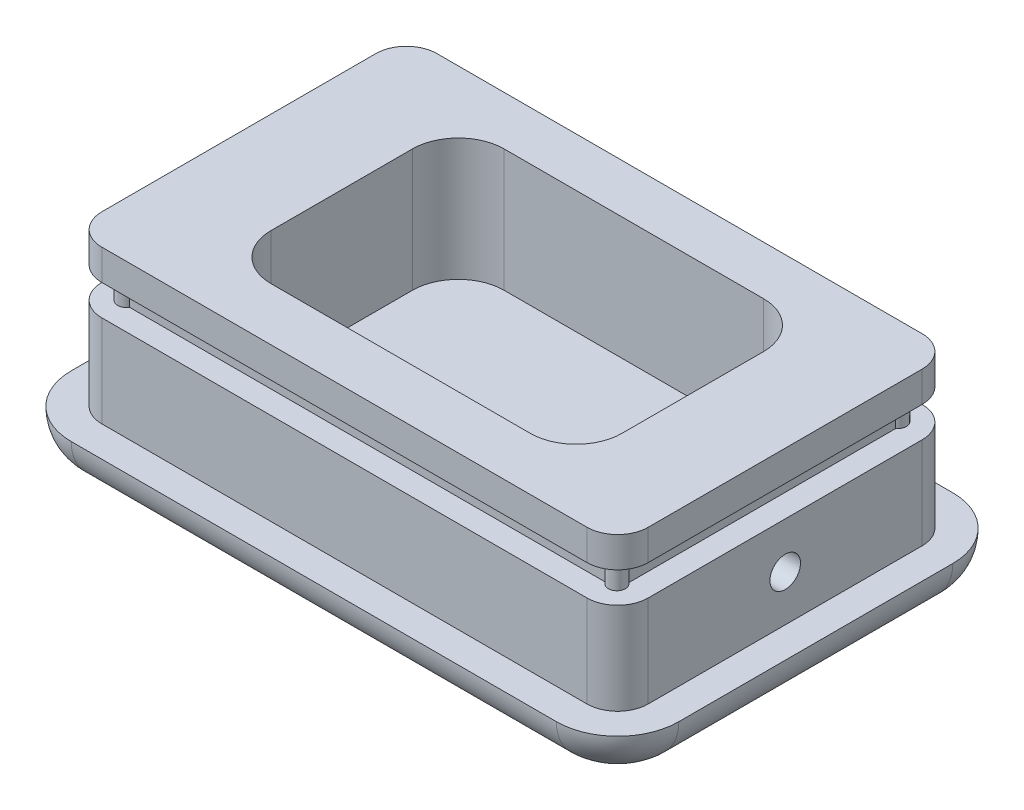
SolidWorks part; units mm, degrees
ref_plane "Alzado" through (0, 0, 0) normal (0, 0, 1) x (1, 0, 0)
ref_plane "Planta" through (0, 0, 0) normal (0, 1, 0) x (1, 0, 0)
ref_plane "Vista lateral" through (0, 0, 0) normal (1, 0, 0) x (0, 0, -1)
sketch "Croquis1" plane through (0, 0, 0) normal (0, 1, 0) x (1, 0, 0)
  line L0 (0, 47.449) -> (0, -64.3311) construction
  line L1 (-97.328, 0) -> (118.047, 0) construction
  line L7 (-15.85, -12.95) -> (15.85, -12.95)
  line L8 (-19.85, -8.95) -> (-19.85, 8.95)
  line L9 (-15.85, 12.95) -> (15.85, 12.95)
  line L10 (19.85, -8.95) -> (19.85, 8.95)
  line L11 (-19.85, -12.95) -> (19.85, 12.95) construction
  line L12 (-19.85, 12.95) -> (19.85, -12.95) construction
  arc A4 (15.85, 12.95) -> (19.85, 8.95) centre (15.85, 8.95) cw
  arc A5 (15.85, -12.95) -> (19.85, -8.95) centre (15.85, -8.95) ccw
  arc A6 (-15.85, -12.95) -> (-19.85, -8.95) centre (-15.85, -8.95) cw
  arc A7 (-19.85, 8.95) -> (-15.85, 12.95) centre (-15.85, 8.95) cw
  point P5 (0, 0)
  dimension "D2" = 25.9
  dimension "D3" = 4
  dimension "D1" = 39.7
extrude "Saliente-Extruir1" add sketch "Croquis1" along normal blind 3
sketch "Croquis2" plane through (0, 3, 0) normal (0, 1, 0) x (1, 0, 0)
  line L0 (15.85, 10.95) -> (-15.85, 10.95)
  line L1 (-17.85, 8.95) -> (-17.85, -8.95)
  line L2 (-15.85, -10.95) -> (15.85, -10.95)
  line L3 (17.85, -8.95) -> (17.85, 8.95)
  line L8 (15.85, 11.25) -> (-15.85, 11.25)
  line L9 (-18.15, 8.95) -> (-18.15, -8.95)
  line L10 (-15.85, -11.25) -> (15.85, -11.25)
  line L11 (18.15, -8.95) -> (18.15, 8.95)
  line L12 (15.85, 11.25) -> (-15.85, 11.25) construction
  line L13 (-18.15, 8.95) -> (-18.15, -8.95) construction
  line L14 (-15.85, -11.25) -> (15.85, -11.25) construction
  line L15 (18.15, -8.95) -> (18.15, 8.95) construction
  arc A0 (17.85, 8.95) -> (15.85, 10.95) centre (15.85, 8.95) ccw
  arc A1 (-15.85, 10.95) -> (-17.85, 8.95) centre (-15.85, 8.95) ccw
  arc A2 (-17.85, -8.95) -> (-15.85, -10.95) centre (-15.85, -8.95) ccw
  arc A3 (15.85, -10.95) -> (17.85, -8.95) centre (15.85, -8.95) ccw
  arc A8 (18.15, 8.95) -> (15.85, 11.25) centre (15.85, 8.95) ccw
  arc A9 (-15.85, 11.25) -> (-18.15, 8.95) centre (-15.85, 8.95) ccw
  arc A10 (-18.15, -8.95) -> (-15.85, -11.25) centre (-15.85, -8.95) ccw
  arc A11 (15.85, -11.25) -> (18.15, -8.95) centre (15.85, -8.95) ccw
  arc A12 (18.15, 8.95) -> (15.85, 11.25) centre (15.85, 8.95) ccw construction
  arc A13 (-15.85, 11.25) -> (-18.15, 8.95) centre (-15.85, 8.95) ccw construction
  arc A14 (-18.15, -8.95) -> (-15.85, -11.25) centre (-15.85, -8.95) ccw construction
  arc A15 (15.85, -11.25) -> (18.15, -8.95) centre (15.85, -8.95) ccw construction
  dimension "D1" = 1.7
  dimension "D2" = 0.3
extrude "Saliente-Extruir3" add sketch "Croquis2" along normal blind 6 contours L2 A3 L3 A0 L0 A1 L1 A2
sketch "Croquis3" plane through (0, 9, 0) normal (0, 1, 0) x (1, 0, 0)
  line L8 (-15.85, -9.45) -> (15.85, -9.45)
  line L9 (16.35, -8.95) -> (16.35, 8.95)
  line L10 (15.85, 9.45) -> (-15.85, 9.45)
  line L11 (-16.35, 8.95) -> (-16.35, -8.95)
  line L12 (-15.85, -9.45) -> (15.85, -9.45)
  line L13 (16.35, -8.95) -> (16.35, 8.95)
  line L14 (15.85, 9.45) -> (-15.85, 9.45)
  line L15 (-16.35, 8.95) -> (-16.35, -8.95)
  arc A8 (15.85, -9.45) -> (16.35, -8.95) centre (15.85, -8.95) ccw
  arc A9 (16.35, 8.95) -> (15.85, 9.45) centre (15.85, 8.95) ccw
  arc A10 (-15.85, 9.45) -> (-16.35, 8.95) centre (-15.85, 8.95) ccw
  arc A11 (-16.35, -8.95) -> (-15.85, -9.45) centre (-15.85, -8.95) ccw
  arc A12 (15.85, -9.45) -> (16.35, -8.95) centre (15.85, -8.95) ccw
  arc A13 (16.35, 8.95) -> (15.85, 9.45) centre (15.85, 8.95) ccw
  arc A14 (-15.85, 9.45) -> (-16.35, 8.95) centre (-15.85, 8.95) ccw
  arc A15 (-16.35, -8.95) -> (-15.85, -9.45) centre (-15.85, -8.95) ccw
  dimension "D1" = 1.5
extrude "Saliente-Extruir4" add sketch "Croquis3" along normal blind 2
sketch "Croquis4" plane through (0, 11, 0) normal (0, 1, 0) x (1, 0, 0)
  line L4 (-15.85, -10.95) -> (15.85, -10.95)
  line L5 (17.85, -8.95) -> (17.85, 8.95)
  line L6 (15.85, 10.95) -> (-15.85, 10.95)
  line L7 (-17.85, 8.95) -> (-17.85, -8.95)
  line L8 (-15.85, -10.95) -> (15.85, -10.95)
  line L9 (17.85, -8.95) -> (17.85, 8.95)
  line L10 (15.85, 10.95) -> (-15.85, 10.95)
  line L11 (-17.85, 8.95) -> (-17.85, -8.95)
  arc A4 (15.85, -10.95) -> (17.85, -8.95) centre (15.85, -8.95) ccw
  arc A5 (17.85, 8.95) -> (15.85, 10.95) centre (15.85, 8.95) ccw
  arc A6 (-15.85, 10.95) -> (-17.85, 8.95) centre (-15.85, 8.95) ccw
  arc A7 (-17.85, -8.95) -> (-15.85, -10.95) centre (-15.85, -8.95) ccw
  arc A8 (15.85, -10.95) -> (17.85, -8.95) centre (15.85, -8.95) ccw
  arc A9 (17.85, 8.95) -> (15.85, 10.95) centre (15.85, 8.95) ccw
  arc A10 (-15.85, 10.95) -> (-17.85, 8.95) centre (-15.85, 8.95) ccw
  arc A11 (-17.85, -8.95) -> (-15.85, -10.95) centre (-15.85, -8.95) ccw
  dimension "D1" = 0
extrude "Saliente-Extruir5" add sketch "Croquis4" along normal blind 2
fillet "Redondeo1" radius 3 8 edges at (0, 0, -12.95) (-18.6784, 0, -11.7784) (-19.85, 0, 0) (-18.6784, 0, 11.7784) (0, 0, 12.95) (18.6784, 0, 11.7784) (19.85, 0, 0) (18.6784, 0, -11.7784)
sketch "Croquis5" plane through (-17.85, 0, 0) normal (-1, 0, 0) x (0, 0, 1)
  line L0 (0, 9) -> (0, 3) construction
  line L1 (-8.95, 9) -> (8.95, 9) construction
  line L2 (-8.95, 3) -> (8.95, 3) construction
  circle A0 centre (0, 6) radius 1
  dimension "D1" = 2
extrude "Cortar-Extruir1" cut sketch "Croquis5" against normal blind 5
sketch "Croquis6" plane through (17.85, 0, 0) normal (1, 0, 0) x (0, 0, -1)
  line L0 (0, 9) -> (0, 3) construction
  line L1 (-8.95, 9) -> (8.95, 9) construction
  line L2 (-8.95, 3) -> (8.95, 3) construction
  circle A0 centre (0, 6) radius 1
  dimension "D1" = 2
extrude "Cortar-Extruir2" cut sketch "Croquis6" against normal blind 5
sketch "Croquis8" plane through (0, 13, 0) normal (0, 1, 0) x (1, 0, 0)
  line L0 (-17.85, 0) -> (17.85, 0)
  line L1 (-17.85, 8.95) -> (-17.85, -8.95) construction
  line L2 (17.85, -8.95) -> (17.85, 8.95) construction
  line L3 (0, 10.95) -> (0, -10.95)
  line L4 (15.85, 10.95) -> (-15.85, 10.95) construction
  line L5 (-15.85, -10.95) -> (15.85, -10.95) construction
  arc A0 (-16.35, 8.95) -> (-15.85, 9.45) centre (-16.0274, 9.1274) cw
  arc A1 (16.35, 8.95) -> (15.85, 9.45) centre (16.0274, 9.1274) ccw
  arc A2 (-16.35, -8.95) -> (-15.85, -9.45) centre (-16.0274, -9.1274) ccw
  arc A3 (16.35, -8.95) -> (15.85, -9.45) centre (16.0274, -9.1274) cw
  arc A4 (-16.35, 8.95) -> (-15.85, 9.45) centre (-15.85, 8.95) cw
  arc A5 (15.85, 9.45) -> (16.35, 8.95) centre (15.85, 8.95) cw
  arc A6 (15.85, -9.45) -> (16.35, -8.95) centre (15.85, -8.95) ccw
  arc A7 (-16.35, -8.95) -> (-15.85, -9.45) centre (-15.85, -8.95) ccw
extrude "Saliente-Extruir6" add sketch "Croquis8" against normal blind 5 contours A1 A5 | A6 A3 | A7 A2 | A0 A4
sketch "Croquis9" plane through (0, 13, 0) normal (0, 1, 0) x (1, 0, 0)
  line L1 (-11.2601, 7.7512) -> (11.6791, 7.7512)
  line L2 (-11.2601, 7.7512) -> (-11.2601, -7.4893)
  line L3 (-11.2601, -7.4893) -> (11.6791, -7.4893)
  line L4 (11.6791, 7.7512) -> (11.6791, -7.4893)
extrude "Cortar-Extruir3" cut sketch "Croquis9" against normal blind 8 contours L2 L1 L4 L3
fillet "Redondeo2" radius 3 4 edges at (-11.2601, 9, -7.7512) (11.6791, 9, -7.7512) (11.6791, 9, 7.4893) (-11.2601, 9, 7.4893)
sketch "Croquis11" plane through (0, 9, 0) normal (0, 1, 0) x (1, 0, 0)
  line L0 (-16.35, 8.95) -> (-16.35, -8.95) construction
  line L1 (15.85, 9.45) -> (-15.85, 9.45) construction
  line L2 (0, 10.95) -> (0, -12.95)
  line L3 (15.85, 10.95) -> (-15.85, 10.95) construction
  line L4 (-15.85, -12.95) -> (15.85, -12.95) construction
  line L5 (-19.85, 0) -> (19.85, 0)
  line L6 (-19.85, 8.95) -> (-19.85, -8.95) construction
  line L7 (19.85, -8.95) -> (19.85, 8.95) construction
  arc A0 (-16.35, 8.7223) -> (-15.5451, 9.45) centre (-16.0296, 9.1769) cw
  arc A1 (16.35, 8.7223) -> (15.5451, 9.45) centre (16.0296, 9.1769) ccw
  arc A2 (16.35, -8.7223) -> (15.5451, -9.45) centre (16.0296, -9.1769) cw
  arc A3 (-16.35, -8.7223) -> (-15.5451, -9.45) centre (-16.0296, -9.1769) ccw
  arc A4 (-16.35, 8.7223) -> (-15.5451, 9.45) centre (-15.5837, 8.6837) cw
extrude "Saliente-Extruir13" add sketch "Croquis11" along normal blind 2 contours L0 A3 A0 A1 | L3 A4 A0 L0 L1 | L6 A1 L3 L4 | A2 L6 L7 A0
sketch "Croquis13" plane through (0, 9, 0) normal (0, 1, 0) x (1, 0, 0)
  line L0 (-16.35, 8.95) -> (-16.35, -8.7223) construction
  line L1 (15.5451, 9.45) -> (-15.85, 9.45) construction
  line L2 (-16.35, 8.95) -> (-16.35, 8.4576)
  line L3 (-15.85, 9.45) -> (-15.4136, 9.45)
  arc A0 (-16.35, 8.4576) -> (-15.4136, 9.45) centre (-15.992, 9.0578) cw
  arc A1 (-16.35, 8.95) -> (-15.85, 9.45) centre (-16.0274, 9.1274) cw
extrude "Saliente-Extruir15" add sketch "Croquis13" along normal blind 2 contours L3 A0 L2 A1
